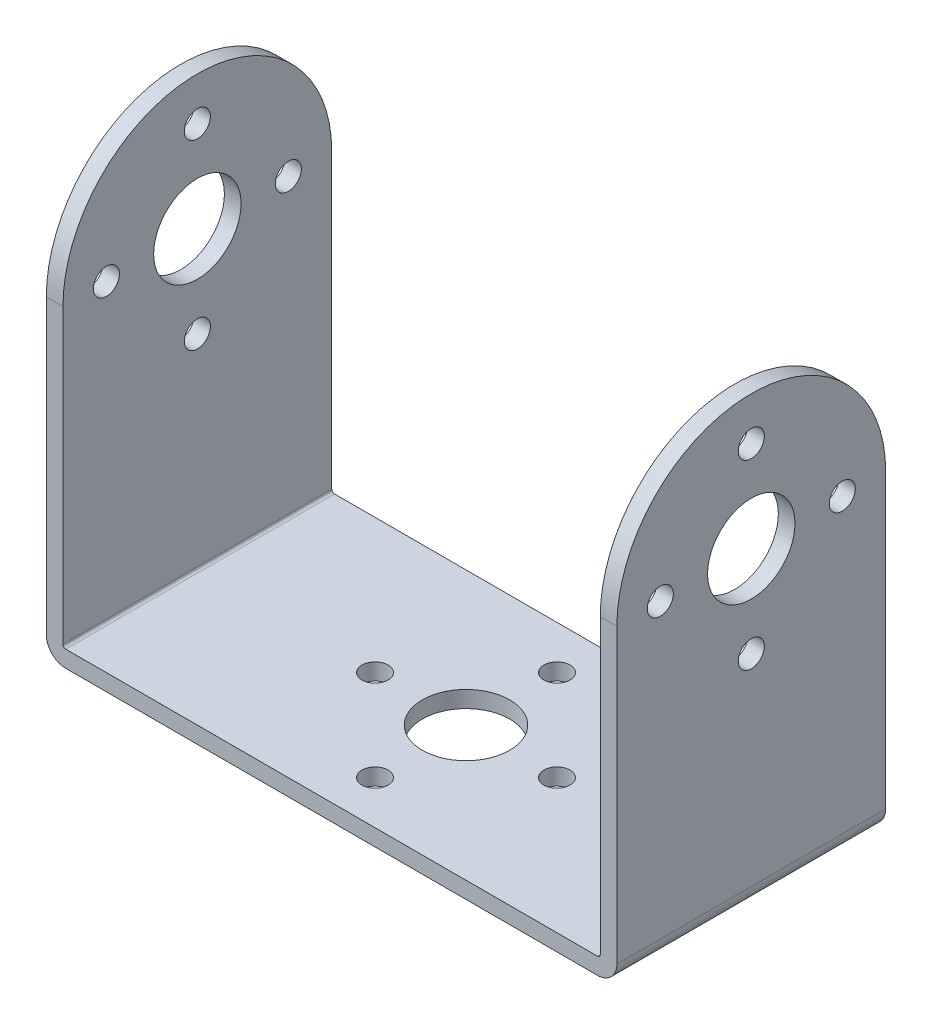
SolidWorks part; units mm, degrees
note: The reader was unsure of these and kept them because the rebuilt part matched: shared geometry of "Sketch1<3>".
ref_plane "Front" through (0, 0, 0) normal (0, 0, 1) x (1, 0, 0)
ref_plane "Top" through (0, 0, 0) normal (0, 1, 0) x (1, 0, 0)
ref_plane "Right" through (0, 0, 0) normal (1, 0, 0) x (0, 0, -1)
sketch "Sketch1" plane through (0, 0, 0) normal (0, 1, 0) x (1, 0, 0)
  line L0 (26.1239, 12.3063) -> (26.1239, -12.3063)
  line L9 (26.1239, -12.3063) -> (-26.1239, -12.3063)
  line L10 (-26.1239, 12.3063) -> (26.1239, 12.3063)
  line L11 (-26.1239, -12.3063) -> (-26.1051, -12.1887)
  line L12 (26.1239, -12.3063) -> (26.1051, -12.1887)
  line L13 (-24.5999, -12.3063) -> (-24.5999, 12.3063)
  line L14 (-26.1239, 12.3063) -> (-26.1239, -12.3063)
  line L15 (24.5999, -12.3063) -> (24.5999, 12.3063)
  circle A5 centre (0, 8.3312) radius 1.1938
  circle A6 centre (-8.3312, 0) radius 1.1938
  circle A7 centre (0, 0) radius 4.0005
  circle A8 centre (8.3312, 0) radius 1.1938
  circle A9 centre (0, -8.3312) radius 1.1938
  point P43 (0, 12.3063)
extrude "Extrude1" add sketch "Sketch1" along normal blind 1.524
extrude "Extrude2" add sketch "Sketch1<3>" along normal blind 40.8686
sketch "Sketch1<3>" plane through (0, 0, 0) normal (0, 1, 0) x (1, 0, 0) same geometry as "Sketch1"
sketch "Sketch4" plane through (0, 0, 0) normal (1, 0, 0) x (0, 0, -1)
  line L0 (-12.3063, 40.8686) -> (-12.3063, 28.5623)
  line L1 (-12.3063, 40.8686) -> (12.3063, 40.8686)
  line L2 (12.3063, 40.8686) -> (12.3063, 28.5623)
  arc A0 (12.3063, 28.5623) -> (-12.3063, 28.5623) centre (0, 28.5623) ccw
  circle A1 centre (0, 28.575) radius 4.0005
  circle A3 centre (0, 36.9062) radius 1.1938
  circle A4 centre (8.3312, 28.575) radius 1.1938
  circle A5 centre (-8.3312, 28.575) radius 1.1938
  circle A6 centre (0, 20.2438) radius 1.1938
extrude "Cut-Extrude1" cut sketch "Sketch4" against normal blind 40.8686 and the other way blind 40.8686 contours L0 A0 L1 | L1 A0 L2 | A1 | A4 | A3 | A5 | A6
fillet "Fillet1" radius 0.254 2 edges
fillet "Fillet2" radius 1.778 2 edges at (-26.1239, 0, 0) (26.1239, 0, 0)
